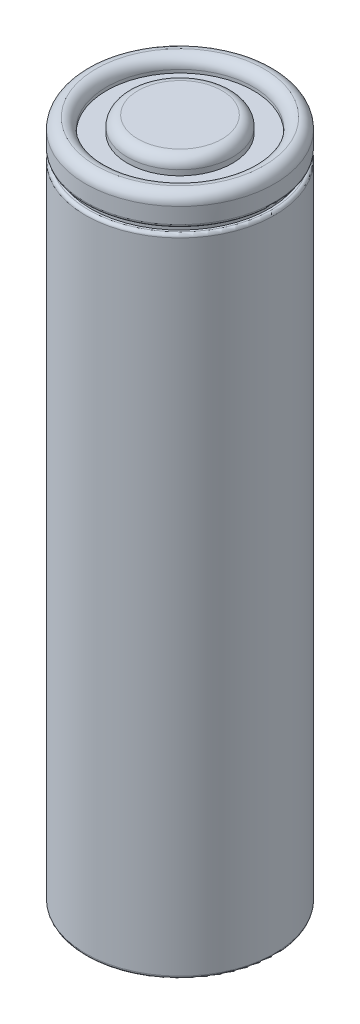
SolidWorks part; units mm, degrees
material "Chrome Stainless Steel"
ref_plane "Front Plane" through (0, 0, 0) normal (0, 0, 1) x (1, 0, 0)
ref_plane "Top Plane" through (0, 0, 0) normal (0, 1, 0) x (1, 0, 0)
ref_plane "Right Plane" through (0, 0, 0) normal (1, 0, 0) x (0, 0, -1)
sketch "Sketch1" plane through (0, 0, 0) normal (0, 1, 0) x (1, 0, 0)
  circle A0 centre (0, 0) radius 9
  dimension "D1" = 18
extrude "Boss-Extrude1" add sketch "Sketch1" along normal blind 65
sketch "Sketch2" plane through (0, 0, 0) normal (0, 0, 1) x (1, 0, 0)
  line L1 (0, 65) -> (0, 0) construction
  line L2 (9, 65) -> (-9, 65) construction
  line L3 (5, 65) -> (5, 63.5)
  line L4 (5, 63.5) -> (7, 63.5)
  line L5 (9, 0) -> (9, 65) construction
  line L6 (7, 63.5) -> (7, 64.8)
  line L7 (8.5, 62) -> (9, 62)
  line L8 (8.5, 62) -> (8.5, 61.5)
  line L9 (8.5, 61.5) -> (9, 61.5)
  line L10 (9, 62) -> (9, 61.5)
  line L11 (7, 64.8) -> (9, 64.8)
  line L12 (9, 64.8) -> (9, 65)
  line L13 (9, 65) -> (5, 65)
  dimension "D1" = 0.5
  dimension "D2" = 0.5
  dimension "D3" = 3
  dimension "D4" = 4
  dimension "D5" = 2
  dimension "D6" = 1.5
  dimension "D7" = 0.2
revolve "Cut-Revolve1" cut sketch "Sketch2" angle 360 about L1
fillet "Fillet1" radius 1 3 edges at (0, 65, 5) (0, 64.8, 7) (0, 64.8, 9)
fillet "Fillet2" radius 0.3 3 edges at (0, 0, 9) (0, 61.5, 9) (0, 62, 9)
equation "\"ABS_thickness\" = 1.59\t"
equation "\"Bus_bar_thickness\" = 3.175"
equation "\"Connector_width\" = 20.2"
equation "\"Number_of_cells_long\" = 25"
equation "\"Number_of_cells_wide\" = 2"
equation "\"Cell_height\" = 65.0"
equation "\"D1@Sketch1\"  = \"Cell_diam\""
equation "\"Cell_diam\" = 18.0"
equation "\"D1@Boss-Extrude1\"=\"Cell_height\""
